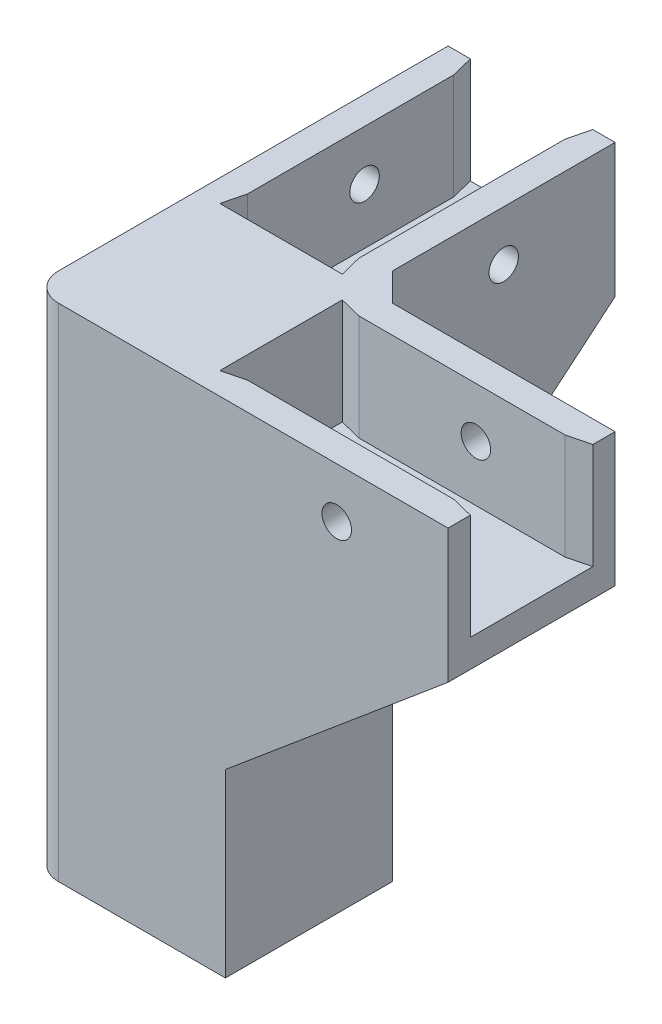
SolidWorks part; units mm, degrees
ref_plane "Front Plane" through (0, 0, 0) normal (0, 0, 1) x (1, 0, 0)
ref_plane "Top Plane" through (0, 0, 0) normal (0, 1, 0) x (1, 0, 0)
ref_plane "Right Plane" through (0, 0, 0) normal (1, 0, 0) x (0, 0, -1)
sketch "Sketch1" plane through (0, 0, 0) normal (0, 1, 0) x (1, 0, 0)
  line L1 (0, 0) -> (75, 0)
  line L2 (0, 0) -> (0, 75)
  line L3 (0, 75) -> (75, 75)
  line L4 (75, 0) -> (75, 75)
  dimension "D1" = 75
  dimension "D2" = 75
extrude "Boss-Extrude1" add sketch "Sketch1" along normal blind 90
sketch "Sketch2" plane through (0, 90, 0) normal (0, 1, 0) x (1, 0, 0)
  line L0 (75, 0) -> (75, 75) construction
  line L17 (75, 5) -> (30, 5)
  line L23 (75, 5) -> (75, 25)
  line L36 (75, 25) -> (30, 25)
  line L37 (30, 5) -> (30, 25)
  line L38 (75, 75) -> (0, 75) construction
  line L39 (5, 75) -> (25, 75)
  line L40 (5, 75) -> (5, 30)
  line L41 (5, 30) -> (25, 30)
  line L42 (25, 75) -> (25, 30)
  line L43 (0, 75) -> (0, 0) construction
  line L44 (0, 0) -> (75, 0) construction
  dimension "D1" = 20
  dimension "D2" = 45
  dimension "D3" = 5
  dimension "D4" = 5
  dimension "D5" = 20
  dimension "D6" = 45
extrude "Cut-Extrude2" cut sketch "Sketch2" against normal blind 19
sketch "Sketch3" plane through (0, 90, 0) normal (0, 1, 0) x (1, 0, 0)
  line L1 (75, 75) -> (30, 75)
  line L2 (75, 75) -> (75, 30)
  line L3 (75, 30) -> (30, 30)
  line L4 (30, 75) -> (30, 30)
  line L5 (75, 25) -> (30, 25) construction
  line L6 (25, 30) -> (25, 75) construction
  dimension "D1" = 5
  dimension "D2" = 5
extrude "Cut-Extrude3" cut sketch "Sketch3" against normal through all
sketch "Sketch4" plane through (0, 0, 0) normal (0, 0, 1) x (1, 0, 0)
  line L0 (35, 32.436) -> (35, 0)
  line L1 (0, 0) -> (75, 0) construction
  line L2 (35, 0) -> (75, 0)
  line L3 (75, 0) -> (75, 66)
  line L4 (75, 66) -> (35, 32.436)
  dimension "D1" = 40
  dimension "D2" = 66
  dimension "D3" = 50
extrude "Cut-Extrude4" cut sketch "Sketch4" against normal through all
sketch "Sketch5" plane through (30, 0, 0) normal (1, 0, 0) x (0, 0, -1)
  line L0 (35, 0) -> (35, 32.436)
  line L1 (75, 0) -> (30, 0) construction
  line L2 (35, 32.436) -> (75, 66)
  line L3 (75, 66) -> (75, 0)
  line L4 (75, 0) -> (35, 0)
  dimension "D1" = 66
  dimension "D2" = 50
  dimension "D3" = 40
extrude "Cut-Extrude5" cut sketch "Sketch5" against normal through all
fillet "Fillet1" radius 5 1 edges at (0, 45, 0)
sketch "Sketch7" plane through (0, 0, -30) normal (0, 0, -1) x (-1, 0, 0)
  line L0 (-30, 90) -> (-75, 90) construction
  line L1 (-75, 66) -> (-75, 90) construction
  circle A0 centre (-55, 81) radius 2.65
  dimension "D3" = 5.3
  dimension "D1" = 9
  dimension "D2" = 20
extrude "Cut-Extrude10" cut sketch "Sketch7" against normal through all both and the other way through all
sketch "Sketch8" plane through (30, 0, 0) normal (1, 0, 0) x (0, 0, -1)
  line L0 (75, 66) -> (75, 90) construction
  line L1 (75, 90) -> (30, 90) construction
  circle A0 centre (55, 81) radius 2.65
  dimension "D3" = 5.3
  dimension "D1" = 20
  dimension "D2" = 9
extrude "Cut-Extrude11" cut sketch "Sketch8" against normal through all both and the other way through all
sketch "Sketch9" plane through (0, 71, 0) normal (0, 1, 0) x (1, 0, 0)
  line L0 (25, 75) -> (5, 75) construction
  line L1 (75, 5) -> (75, 25) construction
  line L2 (30, 5) -> (75, 5) construction
  line L3 (25, 30) -> (25, 75) construction
  circle A0 centre (15, 55) radius 2.65
  circle A1 centre (55, 15) radius 2.65
  dimension "D3" = 5.3
  dimension "D4" = 5.3
  dimension "D1" = 20
  dimension "D2" = 20
  dimension "D5" = 10
  dimension "D6" = 10
extrude "Cut-Extrude12" cut sketch "Sketch9" against normal through all
ref_plane "Plane1" through (0, 66, 0) normal (0, 1, 0) x (1, 0, 0)
sketch "Sketch10" plane through (0, 66, 0) normal (0, 1, 0) x (1, 0, 0)
  circle A0 centre (55, 15) radius 5.5
  circle A1 centre (15, 55) radius 5.5
  dimension "D1" = 11
  dimension "D2" = 11
extrude "Cut-Extrude13" cut sketch "Sketch10" against normal through all
chamfer "Chamfer3" distance 5 angle 45 1 edges at (30, 45, -30)
sketch "Sketch11" plane through (0, 90, 0) normal (0, 1, 0) x (1, 0, 0)
  line L0 (5, 30) -> (4, 30)
  line L1 (4, 30) -> (5, 34)
  line L2 (5, 75) -> (5, 30) construction
  line L3 (5, 34) -> (5, 30)
  line L4 (25, 30) -> (26, 30)
  line L5 (26, 30) -> (25, 34)
  line L6 (25, 30) -> (25, 75) construction
  line L7 (25, 34) -> (25, 30)
  line L8 (30, 25) -> (34, 25)
  line L9 (75, 25) -> (30, 25) construction
  line L10 (34, 25) -> (30, 26)
  line L11 (30, 26) -> (30, 25)
  line L12 (30, 5) -> (30, 4)
  line L13 (30, 4) -> (34, 5)
  line L14 (30, 5) -> (75, 5) construction
  line L15 (34, 5) -> (30, 5)
  line L16 (25, 75) -> (26, 75)
  line L17 (30, 75) -> (25, 75) construction
  line L18 (26, 75) -> (25, 71)
  line L19 (25, 71) -> (25, 75)
  line L20 (5, 71) -> (5, 75)
  line L21 (5, 75) -> (5, 30) construction
  line L22 (5, 75) -> (4, 75)
  line L23 (5, 75) -> (0, 75) construction
  line L24 (4, 75) -> (5, 71)
  line L25 (75, 5) -> (71, 5)
  line L26 (71, 5) -> (75, 4)
  line L27 (75, 0) -> (75, 5) construction
  line L28 (75, 4) -> (75, 5)
  line L29 (71, 25) -> (75, 25)
  line L30 (75, 25) -> (75, 30) construction
  line L31 (75, 25) -> (75, 26)
  line L32 (75, 26) -> (71, 25)
  dimension "D1" = 4
  dimension "D2" = 1
  dimension "D3" = 1
  dimension "D4" = 4
  dimension "D5" = 1
  dimension "D6" = 1
  dimension "D7" = 4
  dimension "D8" = 4
  dimension "D9" = 1
  dimension "D10" = 1
  dimension "D11" = 4
  dimension "D12" = 4
  dimension "D13" = 1
  dimension "D14" = 4
  dimension "D15" = 1
  dimension "D16" = 4
extrude "Cut-Extrude14" cut sketch "Sketch11" against normal up to surface (19 mm away) up to face at (15, 71, -52.35)
